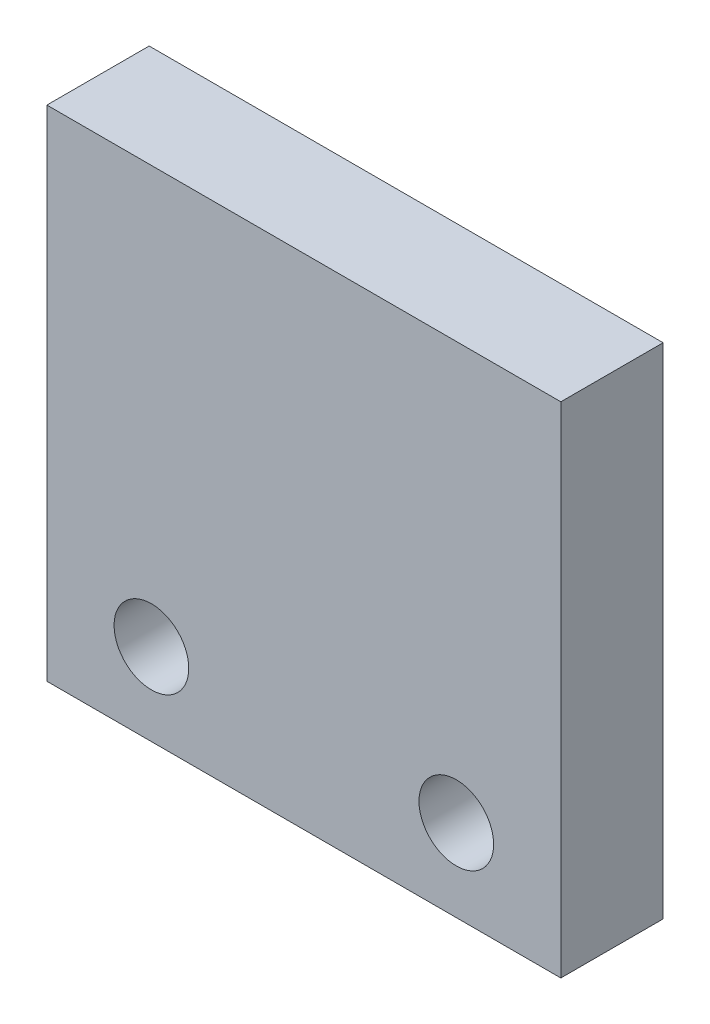
SolidWorks part; units mm, degrees
ref_plane "Front Plane" through (0, 0, 0) normal (0, 0, 1) x (1, 0, 0)
ref_plane "Top Plane" through (0, 0, 0) normal (0, 1, 0) x (1, 0, 0)
ref_plane "Right Plane" through (0, 0, 0) normal (1, 0, 0) x (0, 0, -1)
sketch "Sketch1" plane through (0, 0, 0) normal (0, 0, 1) x (1, 0, 0)
  line L1 (-17.21, 16.71) -> (17.21, 16.71)
  line L3 (-17.21, -16.71) -> (17.21, -16.71)
  line L4 (17.21, 16.71) -> (17.21, -16.71)
  line L5 (0, -16.71) -> (0, 16.71) construction
  line L9 (-17.21, 16.71) -> (-17.21, -16.71)
  circle A0 centre (10.21, -11.21) radius 2.5
  circle A1 centre (-10.21, -11.21) radius 2.5
  point P0 (-17.21, -16.71)
  point P5 (-24.6861, 36.6287)
  point P6 (0, 0)
  dimension "D8" = 5
  dimension "D1" = 34.42
  dimension "D2" = 33.42
  dimension "D6" = 5.5
  dimension "D7" = 7
extrude "Boss-Extrude1" add sketch "Sketch1" along normal blind 6.85
